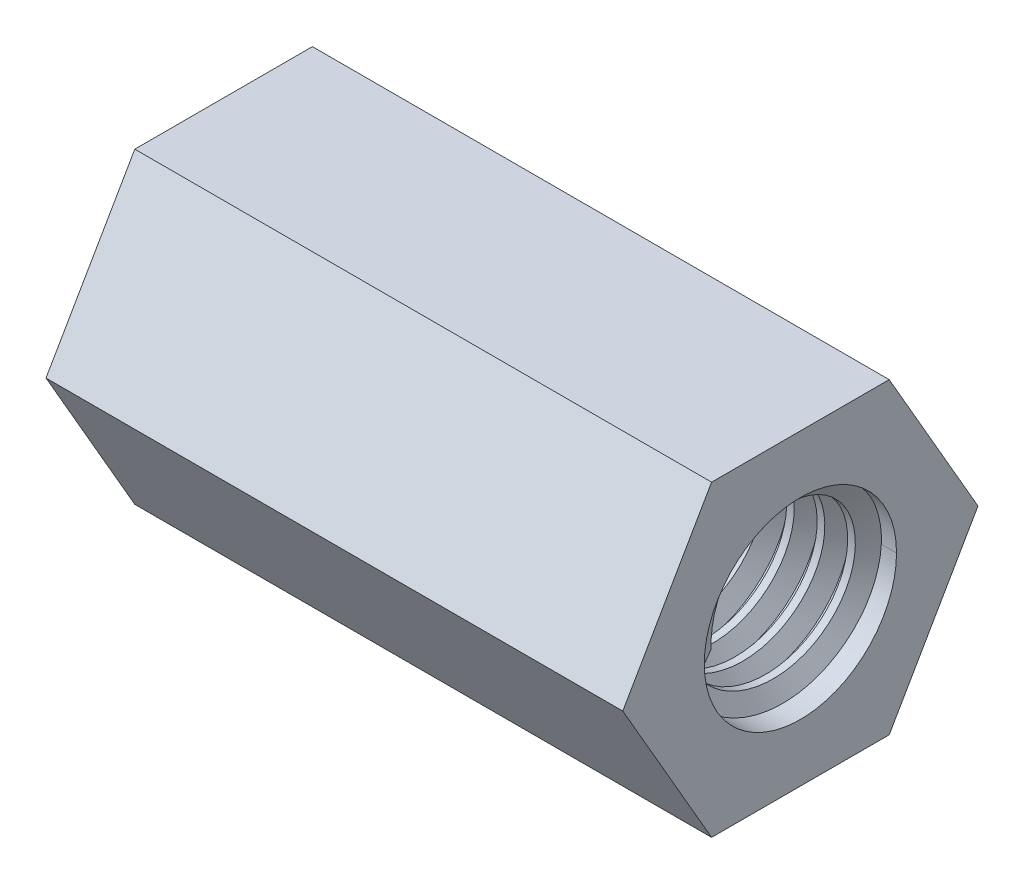
SolidWorks part; units mm, degrees
ref_plane "前视基准面" through (0, 0, 0) normal (0, 0, 1) x (1, 0, 0)
ref_plane "上视基准面" through (0, 0, 0) normal (0, 1, 0) x (1, 0, 0)
ref_plane "右视基准面" through (0, 0, 0) normal (1, 0, 0) x (0, 0, -1)
other "Configuration Table"
sketch "草图1" plane through (0, 0, 0) normal (1, 0, 0) x (0, 0, -1)
  line L1 (0.9238, -1.6) -> (1.8475, 0)
  line L2 (1.8475, 0) -> (0.9238, 1.6)
  line L3 (0.9238, 1.6) -> (-0.9238, 1.6)
  line L4 (-0.9238, 1.6) -> (-1.8475, 0)
  line L5 (-1.8475, 0) -> (-0.9238, -1.6)
  line L6 (-0.9238, -1.6) -> (0.9238, -1.6)
  circle A1 centre (0, 0) radius 1.6 construction
  dimension "D1" = 3.2
extrude "凸台-拉伸2" add sketch "草图1" along normal blind 6
sketch "草图5" plane through (6, 0, 0) normal (1, 0, 0) x (0, 0, -1)
  circle A0 centre (0, 0) radius 1
  dimension "D1" = 2
extrude "切除-拉伸3" cut sketch "草图5" against normal through all
thread "螺纹线1" pitch 0.3175 method extrude profile "螺纹线轮廓1" start angle 0, offset 0, length 5.5, pitch 0.3175, diameter 2
ref_plane "基准面1" through (6, 0, 1) normal (0, -1, 0) x (0, 0, 1)
sketch "螺纹线轮廓1" plane through (6, 0, 1) normal (0, -1, 0) x (0, 0, 1)
  line L0 (0, 0) -> (0, 0.3175) construction
  line L11 (0, 0) -> (0, 0.2778)
  line L12 (0, 0.2778) -> (-0.1719, 0.1786)
  line L13 (-0.1719, 0.1786) -> (-0.1719, 0.0992)
  line L15 (-0.1719, 0.0992) -> (0, 0)
  line L17 (-0.1719, 0.1389) -> (0, 0.1389) construction
  point P2 (0, 0)
  dimension "Pitch" = 0.3175
  dimension "Profile_Angle" = 60
  dimension "Profile_Land" = 0.0794
  dimension "Profile_Height" = 0.1719
